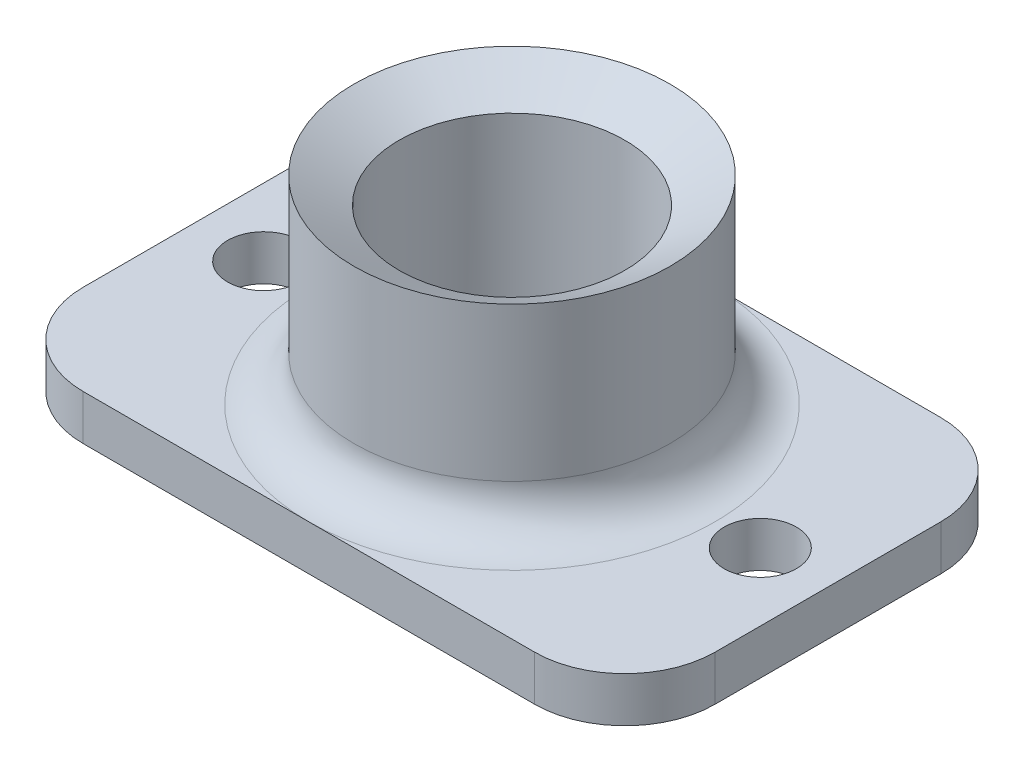
SolidWorks part; units mm, degrees
ref_plane "Alzado" through (0, 0, 0) normal (0, 0, 1) x (1, 0, 0)
ref_plane "Planta" through (0, 0, 0) normal (0, 1, 0) x (1, 0, 0)
ref_plane "Vista lateral" through (0, 0, 0) normal (1, 0, 0) x (0, 0, -1)
sketch "Croquis1" plane through (0, 0, 0) normal (0, 1, 0) x (1, 0, 0)
  line L1 (-35, -22.5) -> (35, -22.5)
  line L2 (-35, -22.5) -> (-35, 22.5)
  line L3 (-35, 22.5) -> (35, 22.5)
  line L4 (35, -22.5) -> (35, 22.5)
  line L5 (-35, -22.5) -> (35, 22.5) construction
  line L6 (-35, 22.5) -> (35, -22.5) construction
  point P0 (0, 0)
  dimension "D1" = 70
  dimension "D2" = 45
extrude "Saliente-Extruir1" add sketch "Croquis1" along normal blind 5
fillet "Redondeo1" radius 10 1 edges at (35, 2.5, 22.5)
fillet "Redondeo2" radius 10 3 edges at (35, 2.5, -22.5) (-35, 2.5, -22.5) (-35, 2.5, 22.5)
sketch "Croquis2" plane through (0, 5, 0) normal (0, 1, 0) x (1, 0, 0)
  circle A0 centre (0, 0) radius 17.5
  dimension "D1" = 35
extrude "Saliente-Extruir2" add sketch "Croquis2" along normal blind 22
fillet "Redondeo3" radius 5 1 edges at (0, 5, 17.5)
sketch "Croquis3" plane through (0, 27, 0) normal (0, 1, 0) x (1, 0, 0)
  circle A0 centre (0, 0) radius 12.5
  dimension "D1" = 25
extrude "Cortar-Extruir1" cut sketch "Croquis3" against normal through all
chamfer "Chaflán1" distance 5 angle 30 1 edges at (0, 27, 12.5) first distance on face at (0, 27, 12.5)
sketch "Croquis4" plane through (0, 0, 0) normal (0, -1, 0) x (-1, 0, 0)
  circle A0 centre (0, 0) radius 14.6
  dimension "D1" = 29.2
extrude "Cortar-Extruir2" cut sketch "Croquis4" against normal blind 2
sketch "Croquis5" plane through (0, 5, 0) normal (0, 1, 0) x (1, 0, 0)
  line L0 (0, 25.7182) -> (0, -27.8803) construction
  line L1 (-41.536, 0) -> (43.243, 0) construction
  circle A0 centre (-27.5, 0) radius 4
  circle A1 centre (27.5, 0) radius 4
  dimension "D1" = 8
  dimension "D2" = 27.5
extrude "Cortar-Extruir3" cut sketch "Croquis5" against normal through all
